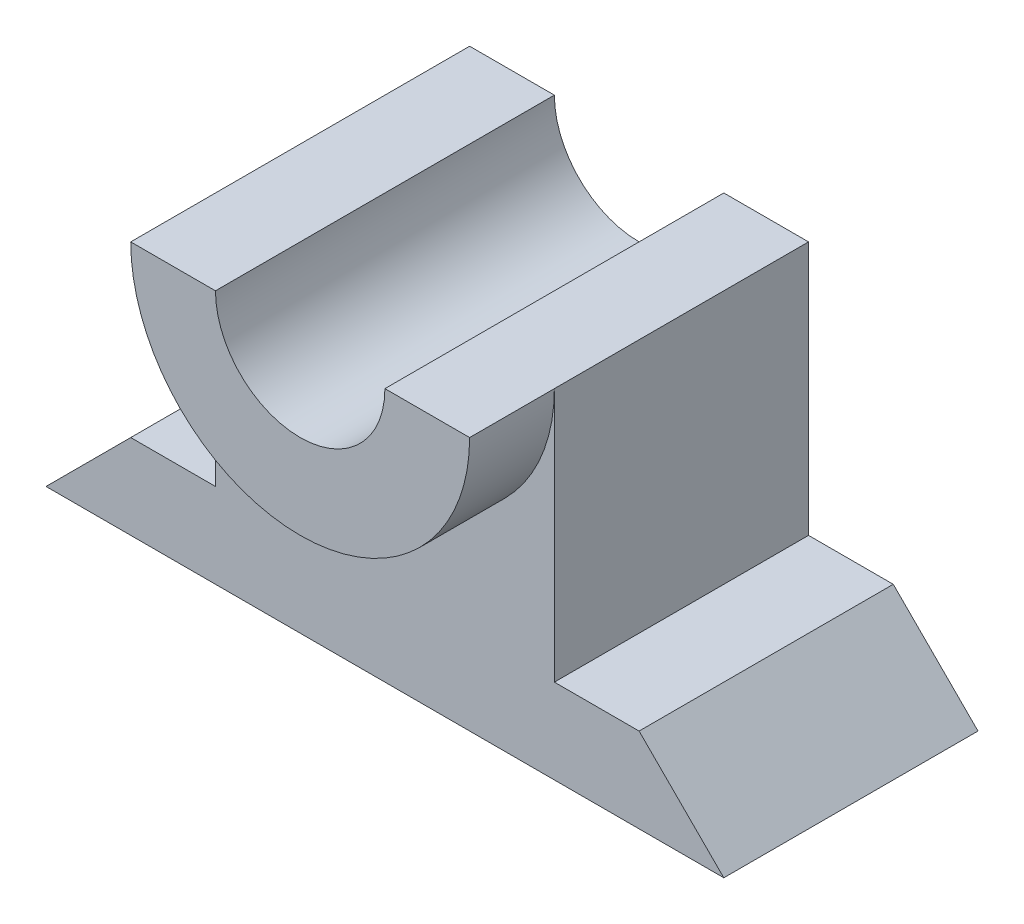
SolidWorks part; units mm, degrees
ref_plane "Front Plane" through (0, 0, 0) normal (0, 0, 1) x (1, 0, 0)
ref_plane "Top Plane" through (0, 0, 0) normal (0, 1, 0) x (1, 0, 0)
ref_plane "Right Plane" through (0, 0, 0) normal (1, 0, 0) x (0, 0, -1)
sketch "Sketch1" plane through (0, 0, 0) normal (0, 0, 1) x (1, 0, 0)
  line L0 (0, 0) -> (0, 979.8661) construction
  line L1 (-1016, 0) -> (1016, 0)
  line L2 (1016, 0) -> (762, 254)
  line L3 (-1016, 0) -> (-762, 254)
  line L4 (762, 254) -> (508, 254)
  line L5 (-762, 254) -> (-508, 254)
  line L6 (508, 254) -> (508, 1016)
  line L7 (-508, 254) -> (-508, 1016)
  line L8 (-508, 1016) -> (-254, 1016)
  line L9 (508, 1016) -> (254, 1016)
  arc A0 (508, 1016) -> (-508, 1016) centre (0, 1016) cw
  arc A1 (254, 1016) -> (-254, 1016) centre (0, 1016) cw
  point P17 (-1637.7155, 20.1925)
  dimension "D5" = 254
  dimension "D6" = 508
  dimension "D1" = 254
  dimension "D2" = 254
  dimension "D3" = 1016
  dimension "D4" = 2032
extrude "Boss-Extrude1" add sketch "Sketch1" along normal blind 1016 contours A0 L0 A1 L8 | L0 A0 L9 A1 region at (-251.5355, 764.4645, 0) region at (251.5355, 764.4645, 0)
extrude "Boss-Extrude2" add sketch "Sketch1<3>" along normal blind 762 contours L1 L0 A0 L7 L5 L3 | L0 L1 L2 L4 L6 A0 region at (-379.4975, 270.3206, 0) region at (379.4975, 270.3206, 0)
sketch "Sketch1<3>" plane through (0, 0, 0) normal (0, 0, 1) x (1, 0, 0) same geometry as "Sketch1"
